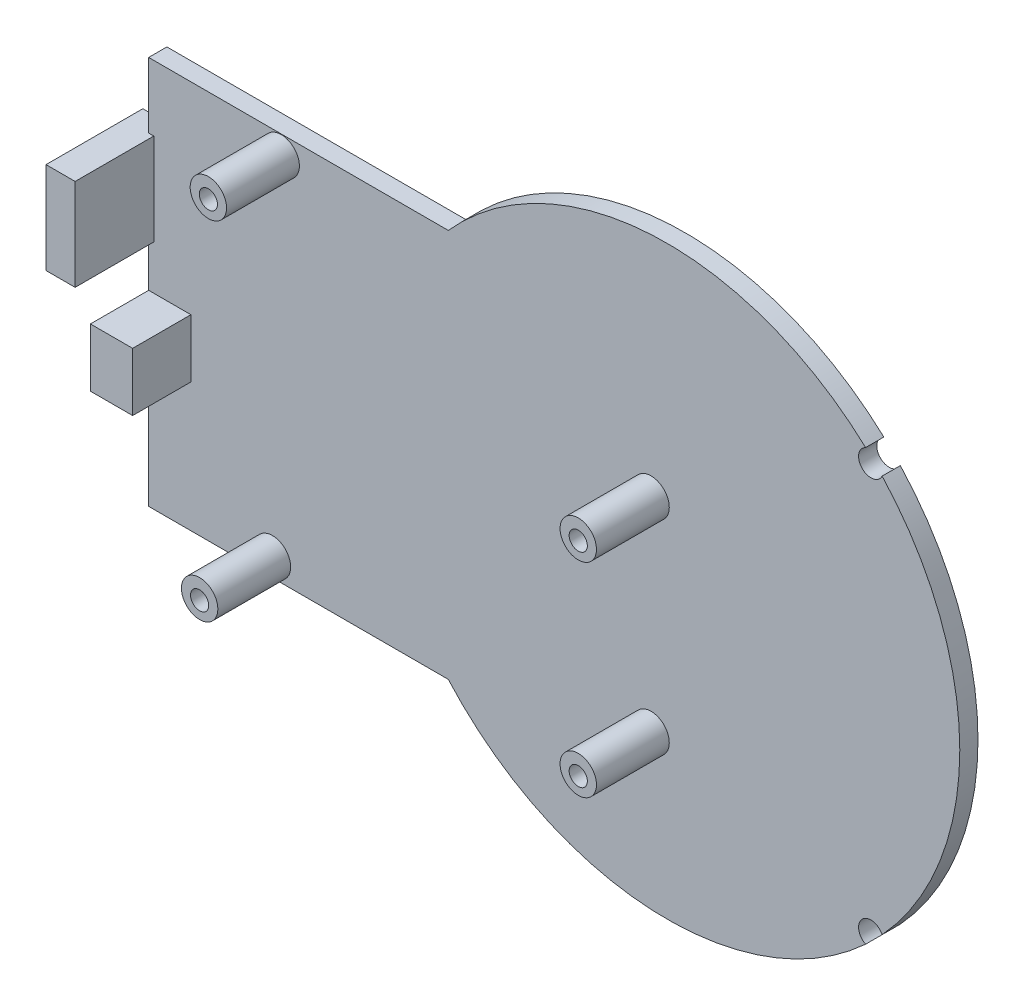
SolidWorks part; units mm, degrees
ref_plane "Front Plane" through (0, 0, 0) normal (0, 0, 1) x (1, 0, 0)
ref_plane "Top Plane" through (0, 0, 0) normal (0, 1, 0) x (1, 0, 0)
ref_plane "Right Plane" through (0, 0, 0) normal (1, 0, 0) x (0, 0, -1)
ref_plane "Plane1" through (0, 0, 6) normal (0, 0, 1) x (1, 0, 0)
sketch "Sketch2" plane through (0, 0, 6) normal (0, 0, 1) x (1, 0, 0)
  line L1 (-71.2, -26.7) -> (-20, -26.7)
  line L2 (-71.2, -26.7) -> (-71.2, 26.7)
  line L3 (-71.2, 26.7) -> (-20, 26.7)
  line L4 (-20, -26.7) -> (-20, 26.7)
extrude "Boss-Extrude2" add sketch "Sketch2" along normal blind 2.5
ref_plane "Plane2" through (0, 0, 8.5) normal (0, 0, 1) x (1, 0, 0)
sketch "Sketch3" plane through (0, 0, 6) normal (0, 0, 1) x (1, 0, 0)
  circle A0 centre (0, 0) radius 40.2
extrude "Boss-Extrude3" add sketch "Sketch3" along normal blind 2.5
sketch "Sketch4" plane through (0, 0, 8.5) normal (0, 0, 1) x (1, 0, 0)
  circle A0 centre (-54.2, -24.17) radius 2.5
  circle A1 centre (-53, 24.13) radius 2.5
  circle A2 centre (-2.2, -19.07) radius 2.5
  circle A3 centre (-2.2, 8.93) radius 2.5
extrude "Boss-Extrude4" add sketch "Sketch4" along normal blind 10
sketch "Sketch5" plane through (0, 0, 8.5) normal (0, 0, 1) x (1, 0, 0)
  line L1 (-71.2, -9) -> (-65.4, -9)
  line L2 (-71.2, -9) -> (-71.2, -1)
  line L3 (-71.2, -1) -> (-65.4, -1)
  line L4 (-65.4, -9) -> (-65.4, -1)
extrude "Boss-Extrude5" add sketch "Sketch5" along normal blind 8
ref_plane "Plane3" through (-71.2, 0, 0) normal (1, 0, 0) x (0, 0, -1)
sketch "Sketch7" plane through (-71.2, 0, 0) normal (1, 0, 0) x (0, 0, -1)
  circle A0 centre (-12.5, -5) radius 2.1
extrude "Cut-Extrude2" cut sketch "Sketch7" along normal blind 5.2
ref_plane "Plane4" through (0, 0, 6) normal (0, 0, 1) x (1, 0, 0)
sketch "Sketch8" plane through (0, 0, 6) normal (0, 0, 1) x (1, 0, 0)
  line L0 (-74.5, 5.1) -> (-70.5, 5.1)
  line L1 (-70.5, 5.1) -> (-70.5, 17.7)
  line L2 (-70.5, 17.7) -> (-74.5, 17.7)
  line L3 (-74.5, 17.7) -> (-74.5, 5.1)
extrude "Boss-Extrude6" add sketch "Sketch8" along normal blind 13.3
sketch "Sketch9" plane through (0, 0, 6) normal (0, 0, 1) x (1, 0, 0)
  circle A0 centre (-54.2, -24.37) radius 1.25
  circle A1 centre (-53, 23.93) radius 1.25
  circle A2 centre (-2.2, -19.27) radius 1.25
  circle A3 centre (-2.2, 8.73) radius 1.25
  circle A4 centre (28, 28) radius 1.7
  circle A5 centre (28, -28) radius 1.7
extrude "Cut-Extrude4" cut sketch "Sketch9" along normal through all
